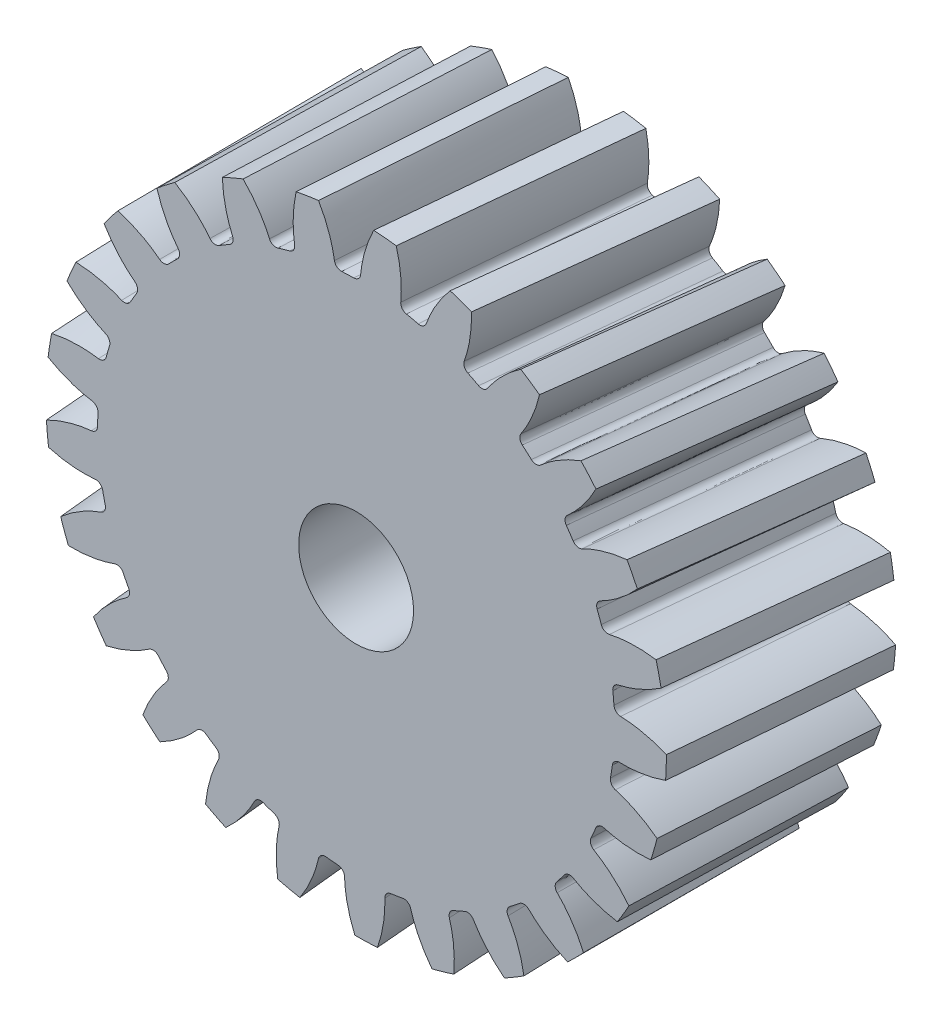
SolidWorks part; units mm, degrees
ref_plane "Płaszczyzna przednia" through (0, 0, 0) normal (0, 0, 1) x (1, 0, 0)
ref_plane "Płaszczyzna górna" through (0, 0, 0) normal (0, 1, 0) x (1, 0, 0)
ref_plane "Płaszczyzna prawa" through (0, 0, 0) normal (1, 0, 0) x (0, 0, -1)
sketch "Sketch1" plane through (0, 0, 0) normal (0, 0, 1) x (1, 0, 0)
  circle A0 centre (0, 0) radius 25
  circle A1 centre (0, 0) radius 27
  circle A2 centre (0, 0) radius 22.5
  circle A3 centre (0, 0) radius 5
  dimension "D1" = 50
  dimension "D2" = 54
  dimension "D3" = 4.5
  dimension "D4" = 10
extrude "Boss-Extrude1" add sketch "Sketch1" along normal mid plane 20 contours A1
sketch "Sketch2" plane through (0, 0, 0) normal (0, 0, 1) x (1, 0, 0)
  line L0 (0, 0) -> (0, 27) construction
  line L1 (-1.5698, 24.9507) -> (1.5698, 24.9507) construction
  line L2 (0, 0) -> (-1.0826, 22.4739) construction
  line L3 (0, 20.6633) -> (-2.6254, 27.8766) construction
  line L4 (0, 0) -> (3.384, 26.7871) construction
  line L5 (1.5698, 24.9507) -> (4.6845, 24.5572) construction
  circle A0 centre (0, 0) radius 27 construction
  arc A1 (-2.9872, 27.8402) -> (-1.0826, 22.4739) centre (-12.048, 21.6032) cw
  arc A2 (2.9872, 27.8402) -> (1.0826, 22.4739) centre (12.048, 21.6032) ccw
  circle A3 centre (0, 0) radius 22.5 construction
  arc A4 (1.0826, 22.4739) -> (-1.0826, 22.4739) centre (0, 0) ccw
  circle A8 centre (0, 0) radius 28
  arc A9 (2.9872, 27.8402) -> (-2.9872, 27.8402) centre (0, 0) ccw
  circle A10 centre (0, 0) radius 25 construction
  circle A11 centre (0, 0) radius 27 construction
  circle A12 centre (0, 0) radius 5 construction
  circle A13 centre (0, 0) radius 5
  dimension "D2" = 20
  dimension "D3" = 7.2
  dimension "D1" = 1
sketch "Sketch3" plane through (0, 0, 0) normal (0, 1, 0) x (1, 0, 0)
  line L0 (-0.8749, -10) -> (0.8749, 10)
  line L1 (-27, -10) -> (27, -10) construction
  line L2 (27, 10) -> (-27, 10) construction
  line L3 (0, -10) -> (0, 10) construction
  dimension "D1" = 5
curve "Curve1"
sketch "Sketch4" plane through (0, 0, 10) normal (0, 0, 1) x (0.9995, 0.0324, 0)
  line L0 (0, 0) -> (0, 27) construction
  line L1 (-1.5698, 24.9507) -> (1.5698, 24.9507) construction
  line L2 (0, 0) -> (-1.0826, 22.4739) construction
  line L3 (0, 20.6633) -> (-2.6254, 27.8766) construction
  line L4 (0, 0) -> (3.384, 26.7871) construction
  line L5 (1.5698, 24.9507) -> (4.6845, 24.5572) construction
  arc A1 (-2.9872, 27.8402) -> (-1.0826, 22.4739) centre (-12.048, 21.6032) cw
  arc A2 (2.9872, 27.8402) -> (1.0826, 22.4739) centre (12.048, 21.6032) ccw
  arc A4 (1.0826, 22.4739) -> (-1.0826, 22.4739) centre (0, 0) ccw
  arc A9 (2.9872, 27.8402) -> (-2.9872, 27.8402) centre (0, 0) ccw
  circle A13 centre (0, 0) radius 5
sketch "Sketch5" plane through (0, 0, -10) normal (0, 0, 1) x (0.9995, -0.0324, 0)
  line L0 (0, 0) -> (0, 27) construction
  line L1 (-1.5698, 24.9507) -> (1.5698, 24.9507) construction
  line L2 (0, 0) -> (-1.0826, 22.4739) construction
  line L3 (0, 20.6633) -> (-2.6254, 27.8766) construction
  line L4 (0, 0) -> (3.384, 26.7871) construction
  line L5 (1.5698, 24.9507) -> (4.6845, 24.5572) construction
  arc A1 (-2.9872, 27.8402) -> (-1.0826, 22.4739) centre (-12.048, 21.6032) cw
  arc A2 (2.9872, 27.8402) -> (1.0826, 22.4739) centre (12.048, 21.6032) ccw
  arc A4 (1.0826, 22.4739) -> (-1.0826, 22.4739) centre (0, 0) ccw
  arc A9 (2.9872, 27.8402) -> (-2.9872, 27.8402) centre (0, 0) ccw
  circle A13 centre (0, 0) radius 5
loft "Cut-Loft1" cut section "Sketch5" section "Sketch2" section "Sketch4" start constraint default end constraint default connector at (3.8877, 27.7288, -10) connector at (2.9872, 27.8402, 0) connector at (2.0835, 27.9224, 10)
fillet "Fillet2" radius 0.6 2 edges
pattern_circular "CirPattern3" count 25 over 360 about axis through (0, 0, 10) along (0, 0, -1) of "Fillet2", "Cut-Loft1"
sketch "Sketch6" plane through (0, 0, 0) normal (0, 0, 1) x (1, 0, 0)
  circle A0 centre (0, 0) radius 5 construction
  circle A1 centre (0, 0) radius 5
extrude "Cut-Extrude2" cut sketch "Sketch6" against normal through all both and the other way through all
equation "\"Module\"= 2mm'Modół"
equation "\"Number of Teeth\"= 25'Liczba zębów"
equation "\"D1@Sketch1\"=\"Module\"*\"Number of Teeth\""
equation "\"D2@Sketch1\"=(\"Number of Teeth\"+2) * \"Module\""
equation "\"D3@Sketch1\"=\"Module\" * if( \"Module\"=>1.25,2.25,2.4)"
equation "\"D3@Sketch2\"=180 / \"Number of Teeth\""
equation "\"angle\" = - 5'Kąt nachylenia zębów"
equation "\"D1@Sketch3\"=\"angle\""
equation "\"D1@Fillet2\"=.3* \"Module\""
equation "\"D1@CirPattern3\"= \"Number of Teeth\""
equation "\"D4@Sketch1\"=(\"Module\"*\"Number of Teeth\") / 5"
